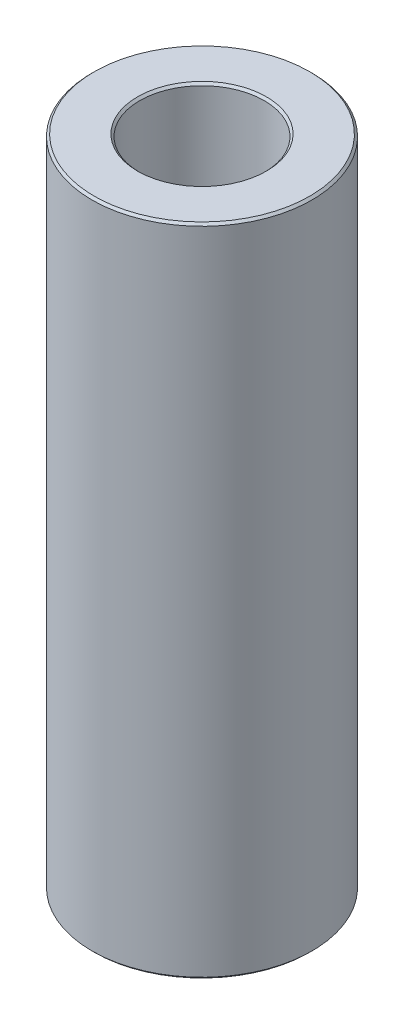
SolidWorks part; units mm, degrees
ref_plane "Front Plane" through (0, 0, 0) normal (0, 0, 1) x (1, 0, 0)
ref_plane "Top Plane" through (0, 0, 0) normal (0, 1, 0) x (1, 0, 0)
ref_plane "Right Plane" through (0, 0, 0) normal (1, 0, 0) x (0, 0, -1)
sketch "Sketch1" plane through (0, 0, 0) normal (0, 1, 0) x (1, 0, 0)
  circle A0 centre (0, 0) radius 42.5
  dimension "SLEEVE_OD" = 85
extrude "Boss-Extrude1" add sketch "Sketch1" along normal blind 252.98
sketch "Sketch2" plane through (0, 0, 0) normal (0, 1, 0) x (1, 0, 0)
  circle A0 centre (0, 0) radius 24.0422
  dimension "BORE_D" = 48.0845
extrude "Cut-Extrude1" cut sketch "Sketch2" along normal through all
chamfer "Chamfer1" distance 0.8542 angle 45 4 edges at (0, 252.98, 24.0422) (0, 0, 24.0422) (0, 0, 42.5) (0, 252.98, 42.5)
